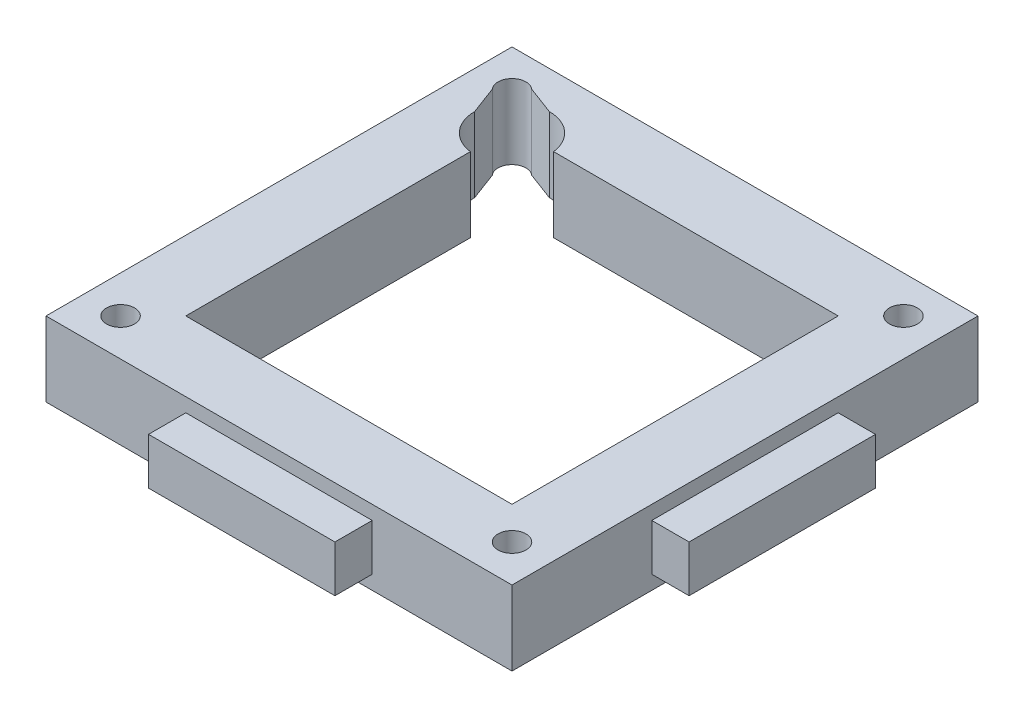
SolidWorks part; units mm, degrees
ref_plane "Front Plane" through (0, 0, 0) normal (0, 0, 1) x (1, 0, 0)
ref_plane "Top Plane" through (0, 0, 0) normal (0, 1, 0) x (1, 0, 0)
ref_plane "Right Plane" through (0, 0, 0) normal (1, 0, 0) x (0, 0, -1)
sketch "Sketch1" plane through (0, 0, 0) normal (0, 1, 0) x (1, 0, 0)
  line L0 (17.5, 17.5) -> (-13.0314, 17.5)
  line L1 (-25, -25) -> (25, -25)
  line L2 (-25, -25) -> (-25, 25)
  line L3 (-25, 25) -> (25, 25)
  line L4 (25, -25) -> (25, 25)
  line L5 (0, 25) -> (0, -25) construction
  line L6 (-25, 0) -> (25, 0) construction
  line L11 (0, 20) -> (0, -20) construction
  line L12 (-20, 0) -> (20, 0) construction
  line L13 (-17.5, -17.5) -> (17.5, -17.5)
  line L16 (17.5, -17.5) -> (17.5, 17.5)
  line L17 (0, 17.5) -> (0, -17.5) construction
  line L18 (-17.5, 0) -> (17.5, 0) construction
  line L19 (-17.5, -17.5) -> (-17.5, 13.0314)
  line L20 (-22.1301, 20.0137) -> (-21, 17)
  line L21 (-20.0137, 22.1301) -> (-17, 21)
  arc A0 (-20.0137, 22.1301) -> (-22.1301, 20.0137) centre (-21, 21) ccw
  circle A1 centre (21, 21) radius 1.5
  circle A2 centre (21, -21) radius 1.5
  circle A3 centre (-21, -21) radius 1.5
  arc A4 (-21, 17) -> (-17, 21) centre (-17, 17) ccw
  point P0 (0, 0)
  point P4 (0, 0)
  point P13 (0, 0)
  dimension "D1" = 50
  dimension "D2" = 50
  dimension "D4" = 35
extrude "Support" add sketch "Sketch1" along normal blind 8 contours L1 L4 L3 L2 A4 L0 L16 L13 L19 L20 A0 L21 A1 A2 A3 region at (-24.2929, 0, 0)
sketch "Sketch2" plane through (0, 0, 0) normal (0, 0, 1) x (1, 0, 0)
  line L4 (-10, 1.5) -> (10, 1.5)
  line L5 (-10, 1.5) -> (-10, 6.5)
  line L6 (-10, 6.5) -> (10, 6.5)
  line L7 (10, 1.5) -> (10, 6.5)
  line L8 (0, 6.5) -> (0, 1.5) construction
  line L9 (-10, 4) -> (10, 4) construction
  point P6 (0, 4)
  dimension "D1" = 20
  dimension "D2" = 5
sketch "Sketch3" plane through (0, 0, 0) normal (1, 0, 0) x (0, 0, -1)
  line L4 (-10, 1.5) -> (10, 1.5)
  line L5 (-10, 1.5) -> (-10, 6.5)
  line L6 (-10, 6.5) -> (10, 6.5)
  line L7 (10, 1.5) -> (10, 6.5)
  line L8 (0, 6.5) -> (0, 1.5) construction
  line L9 (-10, 4) -> (10, 4) construction
  point P6 (0, 4)
  dimension "D1" = 20
  dimension "D2" = 5
extrude "North Cut" cut sketch "Sketch2" along normal blind 4 from surface starting at face at (0, 4, -25)
extrude "South Dowel" add sketch "Sketch2<2>" along normal blind 4 from surface starting at face at (0, 4, 25)
sketch "Sketch2<2>" plane through (0, 0, 0) normal (0, 0, 1) x (1, 0, 0) same geometry as "Sketch2"
extrude "West Dowel" add sketch "Sketch3" along normal blind 4 from surface starting at face at (25, 4, 0)
